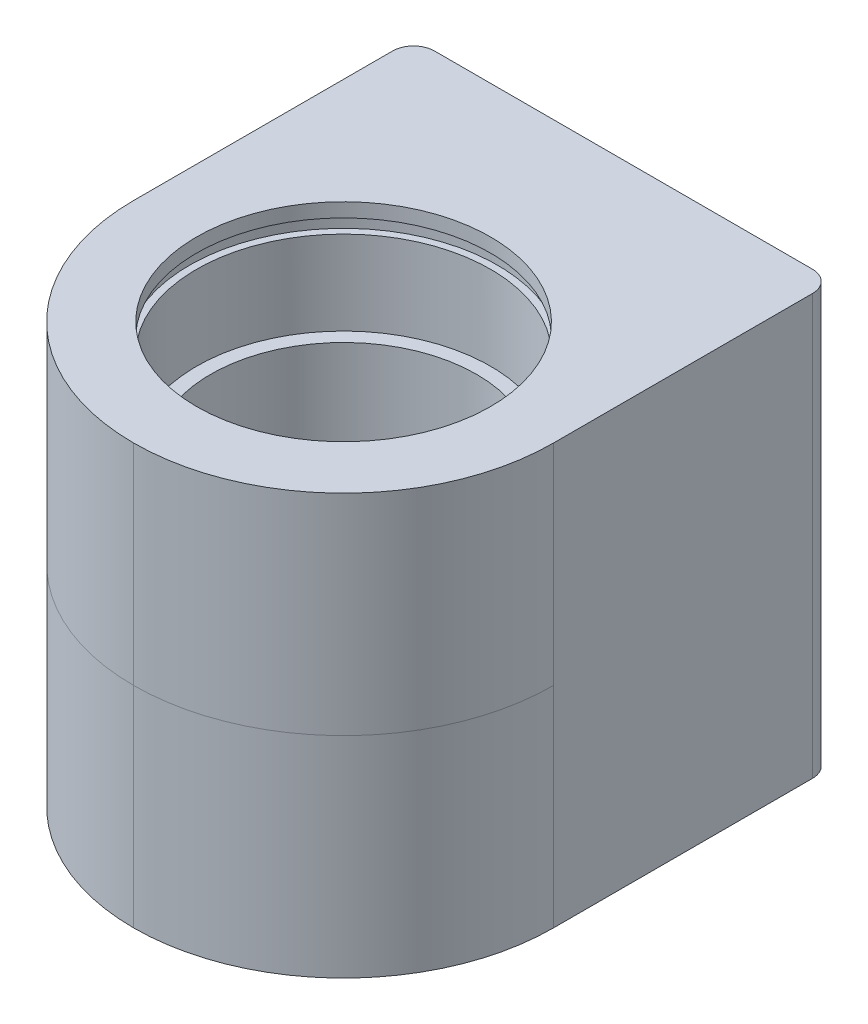
SolidWorks part; units mm, degrees
material "PC - Polycarbonat"
ref_plane "Ebene vorne" through (0, 0, 0) normal (0, 0, 1) x (1, 0, 0)
ref_plane "Ebene oben" through (0, 0, 0) normal (0, 1, 0) x (1, 0, 0)
ref_plane "Ebene rechts" through (0, 0, 0) normal (1, 0, 0) x (0, 0, -1)
sketch "Skizze1" plane through (0, 0, 0) normal (0, 0, 1) x (1, 0, 0)
  line L1 (30, -15) -> (-30, -15)
  line L2 (30, -15) -> (30, 15)
  line L3 (30, 15) -> (-30, 15)
  line L4 (-30, -15) -> (-30, 15)
  line L5 (30, -15) -> (-30, 15) construction
  line L6 (30, 15) -> (-30, -15) construction
  point P0 (0, 0)
  dimension "D1" = 60
  dimension "D2" = 30
extrude "Aufsatz-Linear austragen1" add sketch "Skizze1" along normal blind 70
fillet "Verrundung1" radius 30 2 edges at (30, 0, 70) (-30, 0, 70)
hole_wizard "Stirnsenkung für M42 Zylinderschraube mit Innensechskant1" positions "Skizze2" profile "Skizze3" counterbore size "M42" standard "DIN" end condition through all
sketch "Skizze2" plane through (0, -15, 0) normal (0, -1, 0) x (-1, 0, 0)
  point P0 (0, -40)
  dimension "D1" = 40
sketch "Skizze3" plane through (0, -15, 40) normal (1, 0, 0) x (0, 0, -1)
  line L0 (0, 0) -> (0, 60)
  line L1 (0, 60) -> (19, 60)
  line L3 (19, 60) -> (19, 16)
  line L4 (19, 16) -> (21, 16)
  line L5 (21, 16) -> (21, 0)
  line L7 (21, 0) -> (0, 0)
  line L11 (0, -6.35) -> (0, 107.95) construction
  dimension "Bohrerdurchmesser" = 38
  dimension "Bohrungstiefe" = 60
  dimension "Senkdurchmesser2" = 42
  dimension "Senktiefe2" = 16
ref_plane "Ebene1" through (0, -12, 0) normal (0, 1, 0) x (1, 0, 0)
sketch "Skizze4" plane through (0, -12, 0) normal (0, 1, 0) x (1, 0, 0)
  circle A0 centre (0, -40) radius 22
  dimension "D1" = 44
extrude "Schnitt-Linear austragen1" cut sketch "Skizze4" against normal blind 1 and the other way blind 1
mirror "Spiegeln1" about plane through (30, 15, 70) normal (0, -1, 0) of "Schnitt-Linear austragen1", "Verrundung1", "Aufsatz-Linear austragen1", "Stirnsenkung für M42 Zylinderschraube mit Innensechskant1"
hole_wizard "M6 Gewindebohrung1" positions "Skizze5" profile "Skizze6" tap size "M6" standard "DIN"
sketch "Skizze5" plane through (0, 0, 0) normal (0, 0, -1) x (-1, 0, 0)
  line L0 (-30, -15) -> (-30, 45) construction
  point P0 (-20, 35)
  point P2 (20, 35)
  point P4 (-20, -5)
  point P6 (20, -5)
  point P22 (-30, 15)
  dimension "D1" = 40
  dimension "D2" = 40
  dimension "D3" = 20
  dimension "D4" = 20
sketch "Skizze6" plane through (20, 35, 0) normal (1, 0, 0) x (0, 1, 0)
  line L0 (0, 0) -> (0, 21.5022)
  line L1 (0, 21.5022) -> (2.5, 20)
  line L2 (2.5, 20) -> (2.5, 0)
  line L5 (2.5, 0) -> (0, 0)
  line L10 (0, 21.5022) -> (-2.5, 20) construction
  line L11 (0, -6.35) -> (0, 107.95) construction
  dimension "Bohrerdurchmesser" = 5
  dimension "Bohrungstiefe" = 20
  dimension "Spitzenwinkel" = 118
cosmetic thread "Bohrungsgewinde1" parameters "D1"=15, "D2"=6
cosmetic thread "Bohrungsgewinde2" parameters "D1"=15, "D2"=6
cosmetic thread "Bohrungsgewinde3" parameters "D1"=15, "D2"=6
cosmetic thread "Bohrungsgewinde4" parameters "D1"=15, "D2"=6
fillet "Verrundung2" radius 3 2 edges at (-30, 15, 0) (30, 15, 0)
